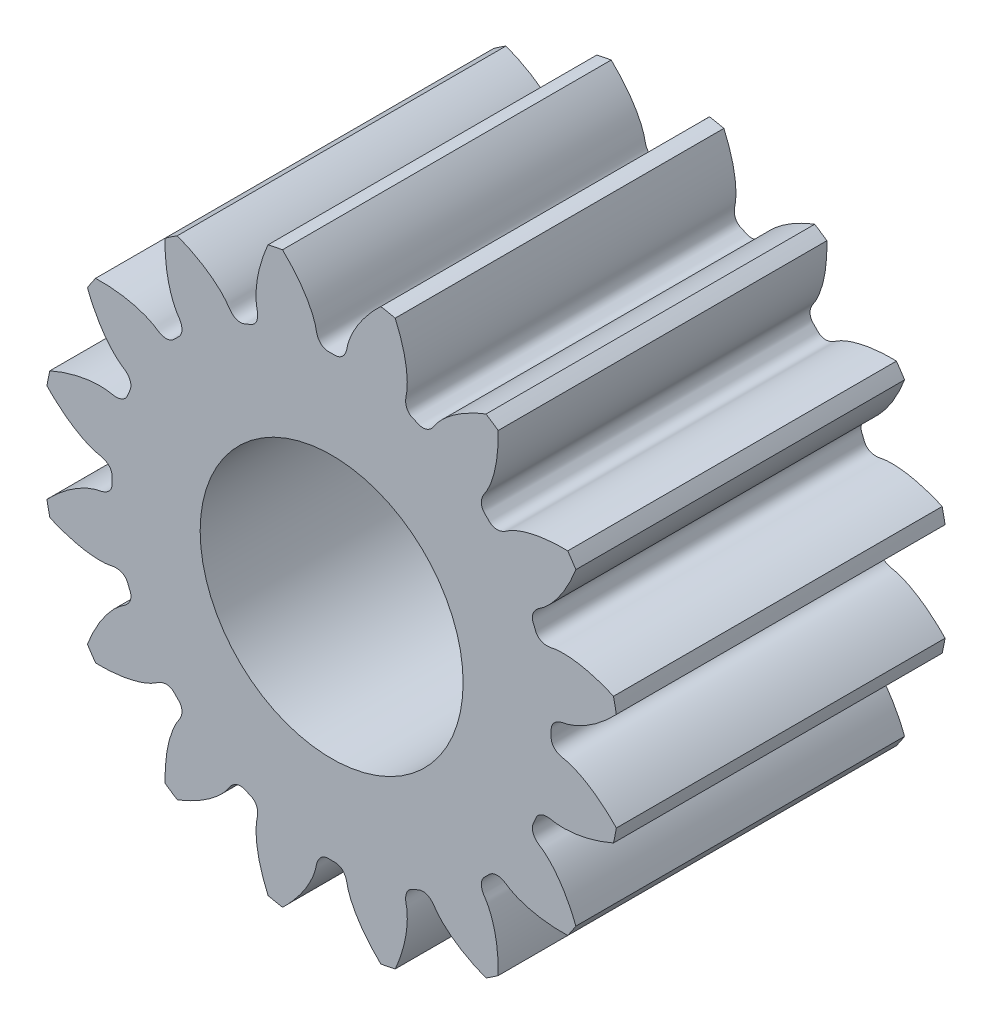
SolidWorks part; units mm, degrees
material "Д16 ГОСТ 4784-97"
ref_plane "FRONT" through (0, 0, 0) normal (0, 0, 1) x (1, 0, 0)
ref_plane "TOP" through (0, 0, 0) normal (0, 1, 0) x (1, 0, 0)
ref_plane "RIGHT" through (0, 0, 0) normal (1, 0, 0) x (0, 0, -1)
ref_axis "Ось1" through (0, 0, 50) along (0, 0, -1)
sketch "SketchRevolveSpurAssemblyNew1Pinion" plane through (0, 0, 0) normal (1, 0, 0) x (0, 0, -1)
  line L0 (0, 0) -> (1, 0) construction
  line L1 (-4, 0) -> (-4, 8.7891)
  line L2 (-4, 8.7891) -> (6, 8.7891)
  line L3 (6, 8.7891) -> (6, 0)
  line L4 (6, 0) -> (-4, 0)
  dimension "D1" = 4
  dimension "D2" = 10
revolve "SpurAssemblyNew1Pinion" add sketch "SketchRevolveSpurAssemblyNew1Pinion" angle 360 about L0
sketch "SketchToothSpurAssemblyNew1Pinion" plane through (0, 0, 0) normal (0, 0, 1) x (1, 0, 0)
  arc A0 (8.716, 1.5542) -> (8.716, -1.5542) centre (0, 0) cw
  spline S0 degree 3 poles (8.716, -1.5542) (8.6286, -1.4593) (8.496, -1.3253) (8.3141, -1.1618) (8.1849, -1.0543) (8.0598, -0.958) (7.9394, -0.8724) (7.8244, -0.797) (7.7153, -0.7313) (7.6127, -0.6747) (7.5171, -0.6266) (7.4291, -0.5864) (7.349, -0.5534) (7.2773, -0.5271) (7.2144, -0.5065) (7.1604, -0.4913) (7.098, -0.4758) (7.0463, -0.4679) (7.0043, -0.4578) (6.9857, -0.4529) (6.9673, -0.4474) (6.9491, -0.4414) (6.9309, -0.4347) (6.9128, -0.4273) (6.8947, -0.4192) (6.8765, -0.4101) (6.8582, -0.3999) (6.8397, -0.3884) (6.821, -0.3754) (6.8021, -0.3606) (6.7831, -0.3437) (6.7641, -0.3241) (6.7455, -0.3015) (6.7276, -0.2756) (6.7111, -0.246) (6.697, -0.2126) (6.6863, -0.1759) (6.68, -0.1381) (6.6779, -0.0791) (6.681, 0) (6.6779, 0.0791) (6.68, 0.1381) (6.6863, 0.1759) (6.697, 0.2126) (6.7111, 0.246) (6.7276, 0.2756) (6.7455, 0.3015) (6.7641, 0.3241) (6.7831, 0.3437) (6.8021, 0.3606) (6.821, 0.3754) (6.8397, 0.3884) (6.8582, 0.3999) (6.8765, 0.4101) (6.8947, 0.4192) (6.9128, 0.4273) (6.9309, 0.4347) (6.9491, 0.4414) (6.9673, 0.4474) (6.9857, 0.4529) (7.0043, 0.4578) (7.0463, 0.4679) (7.098, 0.4758) (7.1604, 0.4913) (7.2144, 0.5065) (7.2773, 0.5271) (7.349, 0.5534) (7.4291, 0.5864) (7.5171, 0.6266) (7.6127, 0.6747) (7.7153, 0.7313) (7.8244, 0.797) (7.9394, 0.8724) (8.0598, 0.958) (8.1849, 1.0543) (8.3141, 1.1618) (8.496, 1.3253) (8.6286, 1.4593) (8.716, 1.5542) knots 0 0 0 0 0.07194 0.10507 0.136308 0.165652 0.193102 0.21866 0.242325 0.264096 0.283974 0.301959 0.318051 0.33225 0.344555 0.354968 0.363487 0.380444 0.384031 0.387599 0.39116 0.394727 0.398315 0.401941 0.405627 0.409398 0.413281 0.41731 0.421523 0.425965 0.430682 0.435726 0.441147 0.446987 0.453273 0.460003 0.467133 0.474573 0.481319 0.5 0.518681 0.525427 0.532867 0.539997 0.546727 0.553013 0.558853 0.564274 0.569318 0.574035 0.578477 0.58269 0.586719 0.590602 0.594373 0.598059 0.601685 0.605273 0.60884 0.612401 0.615969 0.619556 0.636513 0.645032 0.655445 0.66775 0.681949 0.698041 0.716026 0.735904 0.757675 0.78134 0.806898 0.834348 0.863692 0.89493 0.92806 1 1 1 1
extrude "ToothExtrudeCutSpurAssemblyNew1Pinion" cut sketch "SketchToothSpurAssemblyNew1Pinion" against normal blind 8 and the other way blind 4
pattern_circular "PatternSpurAssemblyNew1Pinion" count 16 every 22.5 about axis through (0, 0, 50) along (0, 0, -1) of "ToothExtrudeCutSpurAssemblyNew1Pinion"
sketch "AuxiliarySketchSpurAssemblyNew1Pinion" plane through (0, 0, 0) normal (0, 0, 1) x (1, 0, 0)
  circle A0 centre (0, 0) radius 7.5 construction
  circle A1 centre (0, 0) radius 7.0477 construction
  circle A2 centre (0, 0) radius 7.0831 construction
  circle A3 centre (0, 0) radius 8.7891 construction
  circle A4 centre (0, 0) radius 6.6797 construction
  dimension "PitchDiameter" = 15
  dimension "BaseDiameter" = 14.0954
  dimension "FormDiameter" = 14.1663
  dimension "MajorDiameter" = 17.5781
  dimension "MinorDiameter" = 13.3594
sketch "Эскиз1" plane through (0, 0, 4) normal (0, 0, 1) x (1, 0, 0)
  circle A0 centre (0, 0) radius 4
  dimension "D1" = 8
extrude "Вырез-Вытянуть1" cut sketch "Эскиз1" against normal through all
